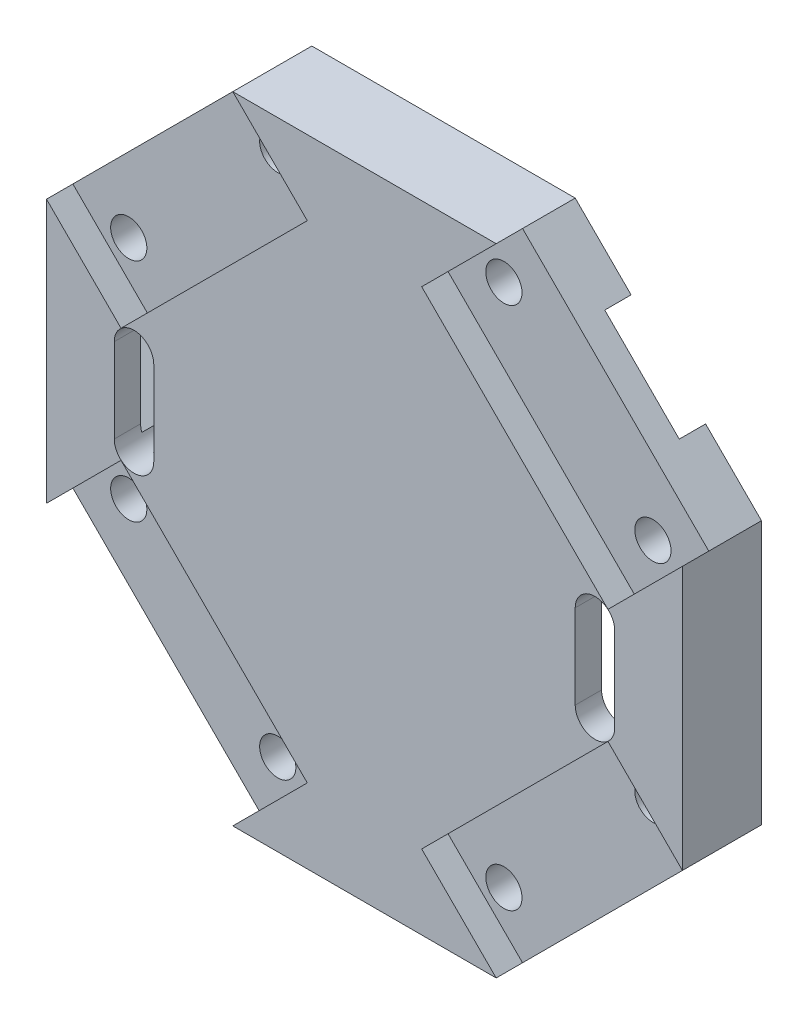
SolidWorks part; units mm, degrees
material "ABS"
ref_plane "Front Plane" through (0, 0, 0) normal (0, 0, 1) x (1, 0, 0)
ref_plane "Top Plane" through (0, 0, 0) normal (0, 1, 0) x (1, 0, 0)
ref_plane "Right Plane" through (0, 0, 0) normal (1, 0, 0) x (0, 0, -1)
sketch "Sketch1" plane through (0, 0, 0) normal (0, 0, 1) x (1, 0, 0)
  line L0 (-38.3256, 15.875) -> (-38.3256, -15.875)
  line L1 (-15.875, -38.3256) -> (15.875, -38.3256)
  line L2 (15.875, -38.3256) -> (38.3256, -15.875)
  line L3 (38.3256, -15.875) -> (38.3256, 15.875)
  line L4 (38.3256, 15.875) -> (15.875, 38.3256)
  line L5 (15.875, 38.3256) -> (-15.875, 38.3256)
  line L6 (-15.875, 38.3256) -> (-38.3256, 15.875)
  line L7 (-38.3256, -15.875) -> (-15.875, -38.3256)
  line L8 (0, 0) -> (0, 37.9758) construction
  circle A0 centre (0, 0) radius 38.3256 construction
  dimension "D1" = 31.75
  dimension "D2" = 15.875
extrude "Boss-Extrude1" add sketch "Sketch1" along normal blind 19.05
ref_plane "Plane1" through (0, 0, 0) normal (1, 0, 0) x (0, 0, -1)
ref_plane "Plane2" through (0, 0, 0) normal (0, 1, 0) x (1, 0, 0)
sketch "Sketch3" plane through (0, 0, 19.05) normal (0, 0, 1) x (1, 0, 0)
  line L0 (-27.1003, 27.1003) -> (-22.6102, 22.6102) construction
  line L1 (-15.875, 38.3256) -> (-38.3256, 15.875) construction
  line L2 (0, 38.3256) -> (0, -38.3256) construction
  line L3 (15.875, 38.3256) -> (-15.875, 38.3256) construction
  line L4 (-15.875, -38.3256) -> (15.875, -38.3256) construction
  line L5 (-38.3256, 0) -> (38.3256, 0) construction
  line L6 (-38.3256, 15.875) -> (-38.3256, -15.875) construction
  line L7 (38.3256, -15.875) -> (38.3256, 15.875) construction
  circle A0 centre (-13.6299, 31.5904) radius 2.1828
  circle A1 centre (31.5904, -13.6299) radius 2.1828
  circle A2 centre (13.6299, -31.5904) radius 2.1828
  circle A3 centre (-13.6299, -31.5904) radius 2.1828
  circle A4 centre (-31.5904, 13.6299) radius 2.1828
  circle A5 centre (13.6299, 31.5904) radius 2.1828
  circle A6 centre (31.5904, 13.6299) radius 2.1828
  circle A7 centre (-31.5904, -13.6299) radius 2.1828
  dimension "D1" = 12.7
  dimension "D3" = 90
  dimension "D4" = 4.3656
  dimension "D2" = 6.35
  dimension "D5" = 6.35
extrude "Cut-Extrude2" cut sketch "Sketch3" against normal through all
sketch "Sketch5" plane through (0, 0, 0) normal (0, 0, -1) x (-1, 0, 0)
  line L0 (0, -35.921) -> (35.921, 0)
  line L1 (0, -35.921) -> (-35.921, 0)
  line L2 (35.921, 0) -> (0, 35.921)
  line L3 (-35.921, 0) -> (0, 35.921)
  line L4 (0, 61.8276) -> (0, -60.2708) construction
  line L5 (0, 4.3656) -> (0, -4.3656) construction
  dimension "D1" = 50.8
  dimension "D2" = 50.8
  dimension "D3" = 25.4
  dimension "D4" = 25.4
  dimension "D5" = 90
  dimension "D6" = 0
sketch "Sketch6" plane through (-27.1003, -27.1003, 0) normal (-0.7071, -0.7071, 0) x (0, 0, 1)
  line L0 (19.05, -38.3256) -> (0, -38.3256) construction
  line L1 (19.05, 38.3256) -> (9.525, 38.3256)
  line L2 (19.05, 38.3256) -> (19.05, -38.3256)
  line L3 (19.05, -38.3256) -> (9.525, -38.3256)
  line L4 (9.525, 38.3256) -> (9.525, -38.3256)
extrude "Cut-Extrude3" cut sketch "Sketch6" against normal through all
extrude "Cut-Extrude4" cut sketch "Sketch5" against normal blind 6.35
sketch "Sketch7" plane through (27.1003, 27.1003, 0) normal (0.7071, 0.7071, 0) x (0, 0, -1)
  line L0 (0, -15.875) -> (0, 15.875) construction
  line L1 (0, 6.35) -> (-3.175, 6.35)
  line L2 (0, 6.35) -> (0, -6.35)
  line L3 (0, -6.35) -> (-3.175, -6.35)
  line L4 (-3.175, 6.35) -> (-3.175, -6.35)
  line L5 (-9.525, 15.875) -> (0, 15.875) construction
  dimension "D1" = 12.7
  dimension "D2" = 9.525
  dimension "D3" = 3.175
extrude "Cut-Extrude5" cut sketch "Sketch7" against normal through all
ref_axis "Axis1" through (0, 0, 8.3344) along (0, 0, -1)
pattern_circular "CirPattern1" count 2 every 90 about axis through (0, 0, 8.3344) along (0, 0, -1) of "Cut-Extrude5"
sketch "Sketch12" plane through (0, 0, 9.525) normal (0, 0, 1) x (1, 0, 0)
  line L0 (134.9865, 252.7088) -> (774.9865, 252.7088) construction
  line L1 (-20.0535, 10.0992) -> (-20.0535, -3.8473)
  line L2 (-20.0535, -3.8473) -> (-15.4614, 0.7449)
  line L3 (-15.4614, 0.7449) -> (-15.4614, 10.0992)
  line L4 (-15.4614, 10.0992) -> (-6.2204, 10.0992)
  line L5 (-6.2204, 10.0992) -> (-8.3747, 7.9449)
  line L6 (-8.3747, 7.9449) -> (-3.2723, 7.9449)
  line L7 (-3.2723, 7.9449) -> (3.6443, 14.8615)
  line L8 (3.6443, 14.8615) -> (-15.4614, 14.8615)
  line L9 (-15.4614, 14.8615) -> (-20.0535, 10.0992)
  line L10 (-17.7574, -3.8473) -> (-10.8409, 3.0693)
  line L11 (-10.8409, 3.0693) -> (-5.8235, 3.0693)
  line L12 (-5.8235, 3.0693) -> (-8.3322, 0.5606)
  line L13 (-8.3322, 0.5606) -> (-3.2723, 0.5606)
  line L14 (-3.2723, 0.5606) -> (-3.2723, 5.422)
  line L15 (-3.2723, 5.422) -> (1.1823, 5.422)
  line L16 (1.1823, 5.422) -> (1.1823, 10.0992)
  line L17 (1.1823, 10.0992) -> (5.6026, 14.5195)
  line L18 (5.6026, 14.5195) -> (5.6026, 5.422)
  line L19 (5.6026, 5.422) -> (19.6949, 5.422)
  line L20 (19.6949, 5.422) -> (19.6949, 0.5606)
  line L21 (19.6949, 0.5606) -> (5.6026, 0.5606)
  line L22 (5.6026, 0.5606) -> (1.5292, -3.5128)
  line L23 (1.5292, -3.5128) -> (1.5292, -9.3008)
  line L24 (1.5292, -9.3008) -> (8.0562, -9.3008)
  line L25 (8.0562, -9.3008) -> (12.3703, -13.6149)
  line L26 (12.3703, -13.6149) -> (-3.2723, -13.6149)
  line L27 (-3.2723, -13.6149) -> (-3.2723, -3.5128)
  line L28 (-3.2723, -3.5128) -> (-17.7574, -3.8473)
  line L29 (6.3825, -4.2928) -> (17.9822, -15.8924)
  line L30 (17.9822, -15.8924) -> (24.2253, -15.8924)
  line L31 (24.2253, -15.8924) -> (12.6487, -4.3158)
  line L32 (12.6487, -4.3158) -> (6.3825, -4.2928)
extrude "Cut-Extrude6" [suppressed] cut sketch "Sketch12" against normal through all contours L28 L27 L26 L25 L24 L23 L22 L21 L20 L19 L18 L17 L16 L15 L14 L13 L12 L11 L10 | L8 L9 L1 L2 L3 L4 L5 L6 L7 | L31 L32 L29 L30
sketch "Sketch13" plane through (0, 0, 9.525) normal (0, 0, 1) x (1, 0, 0)
  line L0 (-38.3256, -15.875) -> (-15.875, -38.3256)
  line L1 (-38.3256, -15.875) -> (-29.3454, -6.8947)
  line L2 (-15.875, -38.3256) -> (-6.8947, -29.3454)
  line L3 (-29.3454, -6.8947) -> (-6.8947, -29.3454)
  line L4 (0, 38.3256) -> (0, -38.3256) construction
  line L5 (-15.875, 38.3256) -> (15.875, 38.3256) construction
  line L6 (15.875, -38.3256) -> (-15.875, -38.3256) construction
  line L7 (15.875, -38.3256) -> (6.8947, -29.3454)
  line L8 (29.3454, -6.8947) -> (6.8947, -29.3454)
  line L9 (38.3256, -15.875) -> (29.3454, -6.8947)
  line L10 (38.3256, -15.875) -> (15.875, -38.3256)
  line L11 (-38.3256, 0) -> (38.3256, 0) construction
  line L13 (-38.3256, -15.875) -> (-38.3256, 15.875) construction
  line L14 (38.3256, 15.875) -> (38.3256, -15.875) construction
  line L15 (38.3256, 15.875) -> (15.875, 38.3256)
  line L16 (38.3256, 15.875) -> (29.3454, 6.8947)
  line L17 (29.3454, 6.8947) -> (6.8947, 29.3454)
  line L18 (15.875, 38.3256) -> (6.8947, 29.3454)
  line L19 (-29.3454, 6.8947) -> (-6.8947, 29.3454)
  line L20 (-15.875, 38.3256) -> (-6.8947, 29.3454)
  line L21 (-38.3256, 15.875) -> (-29.3454, 6.8947)
  line L22 (-38.3256, 15.875) -> (-15.875, 38.3256)
  dimension "D1" = 12.7
extrude "Cut-Extrude7" cut sketch "Sketch13" against normal blind 3.175
sketch "Sketch15" plane through (0, 0, 9.525) normal (0, 0, 1) x (1, 0, 0)
  line L0 (0, 38.3256) -> (0, -38.3256) construction
  line L1 (-15.875, 38.3256) -> (15.875, 38.3256) construction
  line L2 (15.875, -38.3256) -> (-15.875, -38.3256) construction
  line L3 (-38.3256, 0) -> (38.3256, 0) construction
  line L4 (-38.3256, -15.875) -> (-38.3256, 15.875) construction
  line L5 (38.3256, 15.875) -> (38.3256, -15.875) construction
  line L6 (-27.7812, -5.08) -> (-27.7812, 5.08) construction
  line L7 (-30.1625, -5.08) -> (-30.1625, 5.08)
  line L8 (-25.4, -5.08) -> (-25.4, 5.08)
  line L9 (27.7812, -5.08) -> (27.7812, 5.08) construction
  line L10 (30.1625, -5.08) -> (30.1625, 5.08)
  line L11 (25.4, -5.08) -> (25.4, 5.08)
  arc A0 (-30.1625, -5.08) -> (-25.4, -5.08) centre (-27.7812, -5.08) ccw
  arc A1 (-25.4, 5.08) -> (-30.1625, 5.08) centre (-27.7812, 5.08) ccw
  arc A2 (30.1625, -5.08) -> (25.4, -5.08) centre (27.7812, -5.08) cw
  arc A3 (25.4, 5.08) -> (30.1625, 5.08) centre (27.7812, 5.08) cw
  point P14 (-27.7812, 0)
  point P21 (27.7812, 0)
  dimension "D1" = 4.7625
  dimension "D2" = 25.4
  dimension "D3" = 5.08
extrude "Cut-Extrude8" cut sketch "Sketch15" against normal through all
